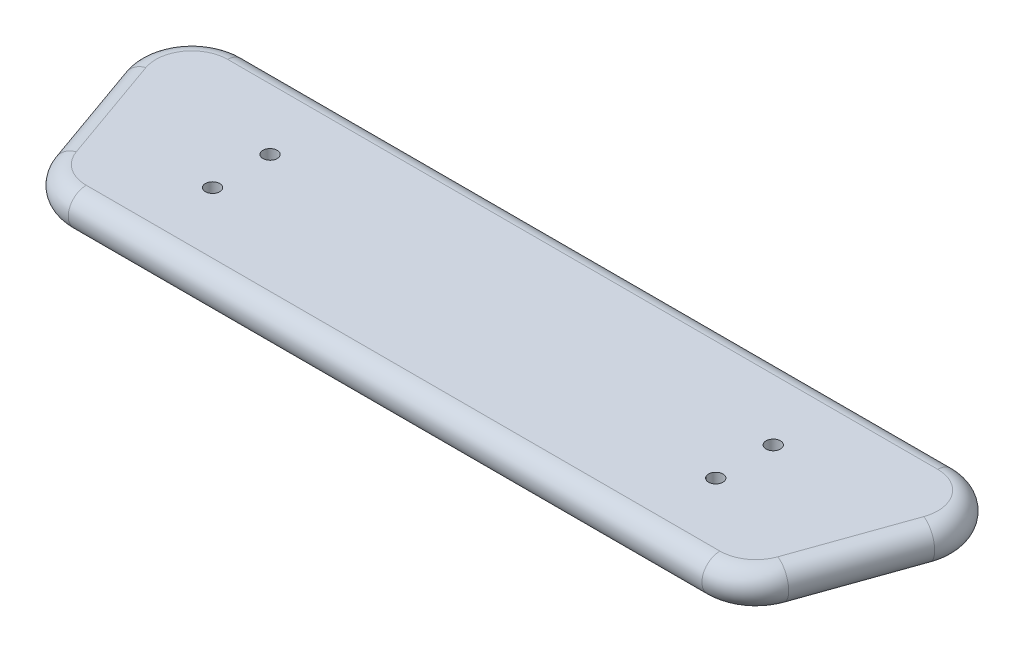
SolidWorks part; units mm, degrees
ref_plane "Front Plane" through (0, 0, 0) normal (0, 0, 1) x (1, 0, 0)
ref_plane "Top Plane" through (0, 0, 0) normal (0, 1, 0) x (1, 0, 0)
ref_plane "Right Plane" through (0, 0, 0) normal (1, 0, 0) x (0, 0, -1)
sketch "Sketch1" plane through (0, 0, 0) normal (0, 1, 0) x (1, 0, 0)
  line L0 (-112.9151, 15) -> (-102.2916, -15)
  line L1 (-98.7755, 35.0071) -> (98.7755, 35.0071)
  line L3 (-88.1519, -24.9929) -> (88.1519, -24.9929)
  line L5 (0, 35.0071) -> (0, 0) construction
  line L6 (0, 0) -> (107.6033, 0) construction
  line L7 (112.9151, 15) -> (102.2916, -15)
  arc A0 (102.2916, -15) -> (88.1519, -24.9929) centre (88.1519, -9.9929) cw
  arc A1 (98.7755, 35.0071) -> (112.9151, 15) centre (98.7755, 20.0071) cw
  arc A2 (-102.2916, -15) -> (-88.1519, -24.9929) centre (-88.1519, -9.9929) ccw
  arc A3 (-98.7755, 35.0071) -> (-112.9151, 15) centre (-98.7755, 20.0071) ccw
  point P0 (0, 0)
  point P13 (120, 35.0071)
  point P18 (-120, 35.0071)
  dimension "D2" = 15
  dimension "D1" = 240
  dimension "D3" = 70.5
  dimension "D4" = 70.5
  dimension "D5" = 60
extrude "Boss-Extrude1" add sketch "Sketch1" along normal blind 10
fillet "Fillet1" 2 edges at (0, 10, 24.9929) (0, 0, 24.9929) type full round first side face at (0, 10, -2.8572) second side face at (0, 0, -2.8572) middle face at (0, 5, 24.9929)
sketch "Sketch5" plane through (0, 0, 0) normal (0, -1, 0) x (1, 0, 0)
  line L0 (0, -5.0071) -> (-80.8226, -5.0071) construction
  line L1 (0, -5.0071) -> (0, 19.9929) construction
  line L2 (88.1519, 19.9929) -> (-88.1519, 19.9929) construction
  circle A0 centre (-70, 2.9929) radius 2
  circle A1 centre (-70, -13.0071) radius 2
  circle A2 centre (70, -13.0071) radius 2
  circle A3 centre (70, 2.9929) radius 2
  dimension "D3" = 4
  dimension "D1" = 30
  dimension "D2" = 8
  dimension "D4" = 70
extrude "Cut-Extrude7" cut sketch "Sketch5" against normal blind 8 from offset 2 offset against normal yes
